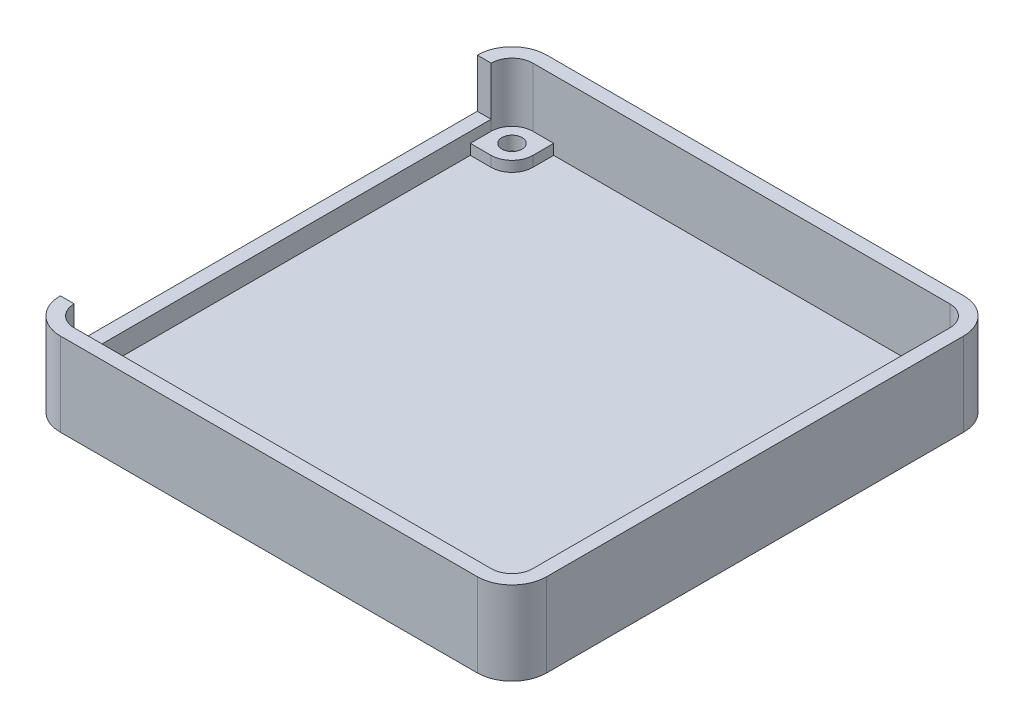
SolidWorks part; units mm, degrees
ref_plane "前视基准面" through (0, 0, 0) normal (0, 0, 1) x (1, 0, 0)
ref_plane "上视基准面" through (0, 0, 0) normal (0, 1, 0) x (1, 0, 0)
ref_plane "右视基准面" through (0, 0, 0) normal (1, 0, 0) x (0, 0, -1)
other "Configuration Table"
sketch "草图1" plane through (0, 0, 0) normal (0, 1, 0) x (1, 0, 0)
  line L1 (-30, -35) -> (30, -35)
  line L2 (-35, -30) -> (-35, 30)
  line L3 (-30, 35) -> (30, 35)
  line L4 (35, -30) -> (35, 30)
  line L5 (-35, -35) -> (35, 35) construction
  line L6 (-35, 35) -> (35, -35) construction
  line L7 (-30, -30) -> (30, -30) construction
  line L8 (-30, -30) -> (-30, 30) construction
  line L9 (-30, 30) -> (30, 30) construction
  line L10 (30, -30) -> (30, 30) construction
  line L11 (-30, -30) -> (30, 30) construction
  line L12 (-30, 30) -> (30, -30) construction
  arc A0 (-30, 35) -> (-35, 30) centre (-30, 30) ccw
  arc A1 (35, 30) -> (30, 35) centre (30, 30) ccw
  arc A2 (30, -35) -> (35, -30) centre (30, -30) ccw
  arc A3 (-35, -30) -> (-30, -35) centre (-30, -30) ccw
  point P0 (0, 0)
  point P6 (0, 0)
  point P14 (0, 0)
  point P20 (0, 0)
  point P21 (0, 0)
  dimension "D1" = 70
  dimension "D2" = 70
  dimension "D3" = 60
extrude "凸台-拉伸1" add sketch "草图1" along normal blind 2
sketch "草图2" plane through (0, 2, 0) normal (0, 1, 0) x (1, 0, 0)
  line L0 (-30, -35) -> (30, -35) construction
  line L1 (-35, 30) -> (-35, -30) construction
  line L2 (30, 35) -> (-30, 35) construction
  line L3 (35, -30) -> (35, 30) construction
  line L4 (-30, -35) -> (30, -35)
  line L5 (-35, 30) -> (-35, -30)
  line L6 (30, 35) -> (-30, 35)
  line L7 (35, -30) -> (35, 30)
  line L8 (-33, -30) -> (-33, 30)
  line L9 (-33, -33) -> (33, -33) construction
  line L10 (-33, -33) -> (-33, 33) construction
  line L11 (-33, 33) -> (33, 33) construction
  line L12 (33, -33) -> (33, 33) construction
  line L13 (-33, -33) -> (33, 33) construction
  line L14 (-33, 33) -> (33, -33) construction
  line L15 (-30, 33) -> (30, 33)
  line L16 (33, 30) -> (33, -30)
  line L17 (30, -33) -> (-30, -33)
  arc A0 (30, -35) -> (35, -30) centre (30, -30) ccw construction
  arc A1 (-35, -30) -> (-30, -35) centre (-30, -30) ccw construction
  arc A2 (-30, 35) -> (-35, 30) centre (-30, 30) ccw construction
  arc A3 (35, 30) -> (30, 35) centre (30, 30) ccw construction
  arc A4 (30, -35) -> (35, -30) centre (30, -30) ccw
  arc A5 (-35, -30) -> (-30, -35) centre (-30, -30) ccw
  arc A6 (-30, 35) -> (-35, 30) centre (-30, 30) ccw
  arc A7 (35, 30) -> (30, 35) centre (30, 30) ccw
  arc A8 (-33, 30) -> (-30, 33) centre (-30, 30) cw
  arc A9 (30, 33) -> (33, 30) centre (30, 30) cw
  arc A10 (33, -30) -> (30, -33) centre (30, -30) cw
  arc A11 (-30, -33) -> (-33, -30) centre (-30, -30) cw
  point P12 (0, 0)
  dimension "D1" = 2
extrude "凸台-拉伸2" add sketch "草图2" along normal blind 10
sketch "草图3" plane through (0, 12, 0) normal (0, 1, 0) x (1, 0, 0)
  line L1 (-33, -30) -> (-35, -30)
  line L2 (-33, -30) -> (-33, 30)
  line L3 (-33, 30) -> (-35, 30)
  line L4 (-35, -30) -> (-35, 30)
extrude "切除-拉伸1" cut sketch "草图3" against normal blind 7
sketch "草图4" plane through (0, 2, 0) normal (0, 1, 0) x (1, 0, 0)
  line L0 (-27, 30) -> (-27, 33)
  line L1 (30, 33) -> (-30, 33) construction
  line L2 (-27, 33) -> (-30, 33)
  line L3 (-30, 27) -> (-33, 27)
  line L4 (-33, -30) -> (-33, 30) construction
  line L5 (-33, 27) -> (-33, 30)
  line L6 (27, 30) -> (27, 33)
  line L7 (27, 33) -> (30, 33)
  line L8 (30, 27) -> (33, 27)
  line L9 (33, -30) -> (33, 30) construction
  line L10 (33, 27) -> (33, 30)
  line L11 (-33, -27) -> (-33, -30)
  line L12 (-30, -33) -> (30, -33) construction
  line L13 (-30, -33) -> (-27, -33)
  line L14 (33, -30) -> (33, -27)
  line L15 (-27, -30) -> (-27, -33)
  line L16 (-30, -27) -> (-33, -27)
  line L18 (33, -27) -> (30, -27)
  line L19 (27, -30) -> (27, -33)
  line L20 (27, -33) -> (30, -33)
  arc A0 (27, 30) -> (30, 27) centre (30, 30) ccw
  arc A1 (-30, 33) -> (-33, 30) centre (-30, 30) ccw
  arc A2 (-27, -30) -> (-30, -27) centre (-30, -30) ccw
  arc A4 (-30, 27) -> (-27, 30) centre (-30, 30) ccw
  arc A5 (33, 30) -> (30, 33) centre (30, 30) ccw
  arc A6 (-33, -30) -> (-30, -33) centre (-30, -30) ccw
  arc A7 (30, -33) -> (33, -30) centre (30, -30) ccw
  arc A8 (30, -27) -> (27, -30) centre (30, -30) ccw
extrude "凸台-拉伸3" add sketch "草图4" along normal blind 1.5
sketch "草图5" plane through (0, 3.5, 0) normal (0, 1, 0) x (1, 0, 0)
  circle A0 centre (30, -30) radius 1.45
  circle A1 centre (30, 30) radius 1.45
  circle A2 centre (-30, 30) radius 1.45
  circle A3 centre (-30, -30) radius 1.45
  dimension "D1" = 2.9
extrude "切除-拉伸2" cut sketch "草图5" against normal blind 2
